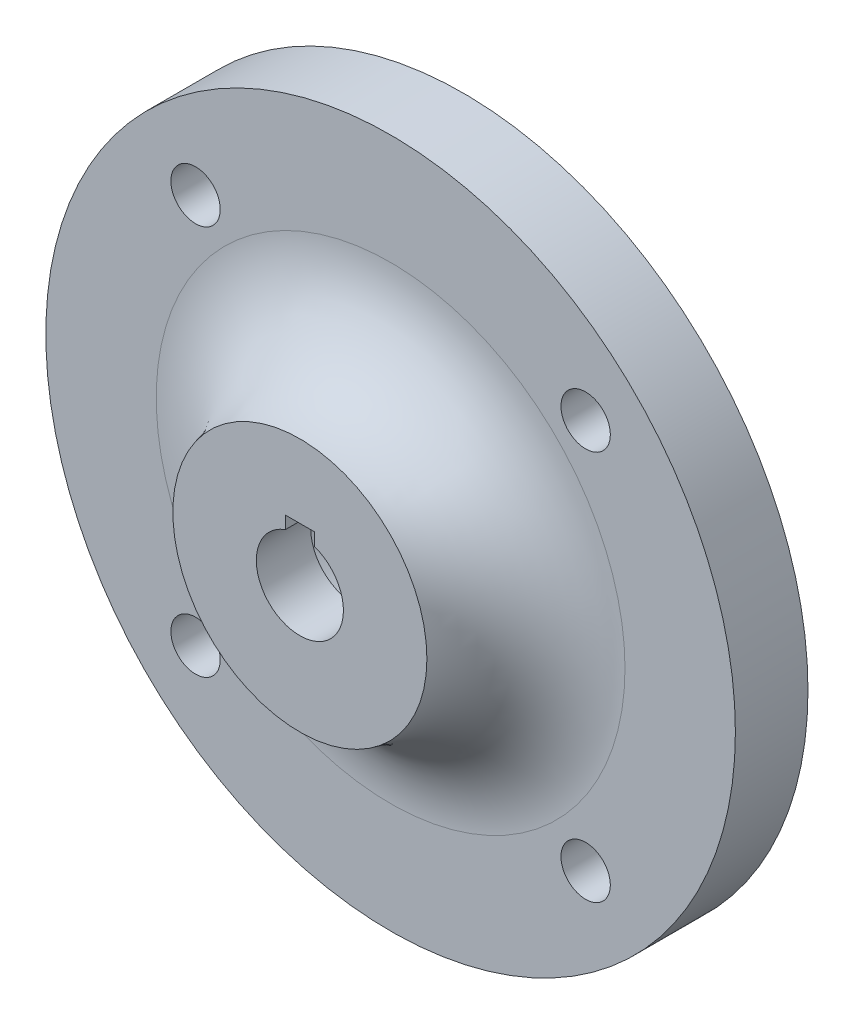
SolidWorks part; units mm, degrees
material "6061-T6 (SS)"
ref_plane "Front Plane" through (0, 0, 0) normal (0, 0, 1) x (1, 0, 0)
ref_plane "Top Plane" through (0, 0, 0) normal (0, 1, 0) x (1, 0, 0)
ref_plane "Right Plane" through (0, 0, 0) normal (1, 0, 0) x (0, 0, -1)
sketch "Spacing" plane through (0, 0, 0) normal (0, 0, 1) x (1, 0, 0)
  line L1 (-26.8701, -26.8701) -> (26.8701, -26.8701)
  line L2 (-26.8701, -26.8701) -> (-26.8701, 26.8701)
  line L3 (-26.8701, 26.8701) -> (26.8701, 26.8701)
  line L4 (26.8701, -26.8701) -> (26.8701, 26.8701)
  line L5 (-26.8701, -26.8701) -> (26.8701, 26.8701) construction
  line L6 (-26.8701, 26.8701) -> (26.8701, -26.8701) construction
  point P0 (0, 0)
  dimension "D1" = 76
sketch "Sketch1" plane through (0, 0, 7) normal (0, 0, 1) x (1, 0, 0)
  circle A4 centre (0, 0) radius 47.5
  circle A6 centre (26.8701, -26.8701) radius 3.4
  circle A7 centre (-26.8701, -26.8701) radius 3.4
  circle A8 centre (-26.8701, 26.8701) radius 3.4
  circle A9 centre (26.8701, 26.8701) radius 3.4
  dimension "D1" = 95
  dimension "D2" = 6.8
extrude "Boss-Extrude1" add sketch "Sketch1" along normal blind 10 from offset 2
sketch "Sketch7" plane through (0, 0, 9) normal (0, 0, -1) x (-1, 0, 0)
  circle A1 centre (26.8701, -26.8701) radius 3.4
  circle A2 centre (26.8701, -26.8701) radius 8
  circle A3 centre (-26.8701, -26.8701) radius 8
  circle A4 centre (-26.8701, -26.8701) radius 3.4
  circle A5 centre (-26.8701, 26.8701) radius 8
  circle A6 centre (-26.8701, 26.8701) radius 3.4
  circle A7 centre (26.8701, 26.8701) radius 8
  circle A8 centre (26.8701, 26.8701) radius 3.4
  circle A9 centre (26.8701, -26.8701) radius 3.4 construction
  point P1 (26.8701, -26.8701)
  point P4 (-26.8701, -26.8701)
  point P6 (-26.8701, 26.8701)
  point P15 (-26.8701, 26.8701)
  point P17 (-26.8701, 26.8701)
  point P21 (-26.8701, -26.8701)
  dimension "D1" = 16
  dimension "D2" = 2
  dimension "D3" = 2
extrude "Boss-Extrude3" add sketch "Sketch7" along normal blind 1
sketch "Sketch3" plane through (0, 0, 19) normal (0, 0, 1) x (1, 0, 0)
  circle A0 centre (0, 0) radius 17.5
  dimension "D1" = 35
extrude "Boss-Extrude2" add sketch "Sketch3" along normal blind 12.5
sketch "Sketch2" plane through (0, 0, 9) normal (0, 0, -1) x (-1, 0, 0)
  circle A0 centre (0, 0) radius 15
  dimension "D1" = 30
extrude "Cut-Extrude1" cut sketch "Sketch2" against normal blind 15
fillet "Fillet1" radius 15 1 edges at (17.5, 0, 19)
sketch "Sketch4" plane through (0, 0, 31.5) normal (0, 0, 1) x (1, 0, 0)
  circle A0 centre (0, 0) radius 6
  dimension "D1" = 12
extrude "Cut-Extrude2" cut sketch "Sketch4" against normal through all
sketch "Sketch5" plane through (0, 0, 31.5) normal (0, 0, 1) x (1, 0, 0)
  line L1 (2, 7.4) -> (-2, 7.4)
  line L2 (2, 7.4) -> (2, 5.6569)
  line L3 (2, 5.6569) -> (-2, 5.6569)
  line L4 (-2, 7.4) -> (-2, 5.6569)
  line L5 (2, 7.4) -> (-2, 5.6569) construction
  line L6 (2, 5.6569) -> (-2, 7.4) construction
  circle A0 centre (0, 0) radius 6 construction
  point P0 (0, 6.5284)
  dimension "D1" = 4
  dimension "D2" = 1.4
extrude "Cut-Extrude3" cut sketch "Sketch5" against normal through all
